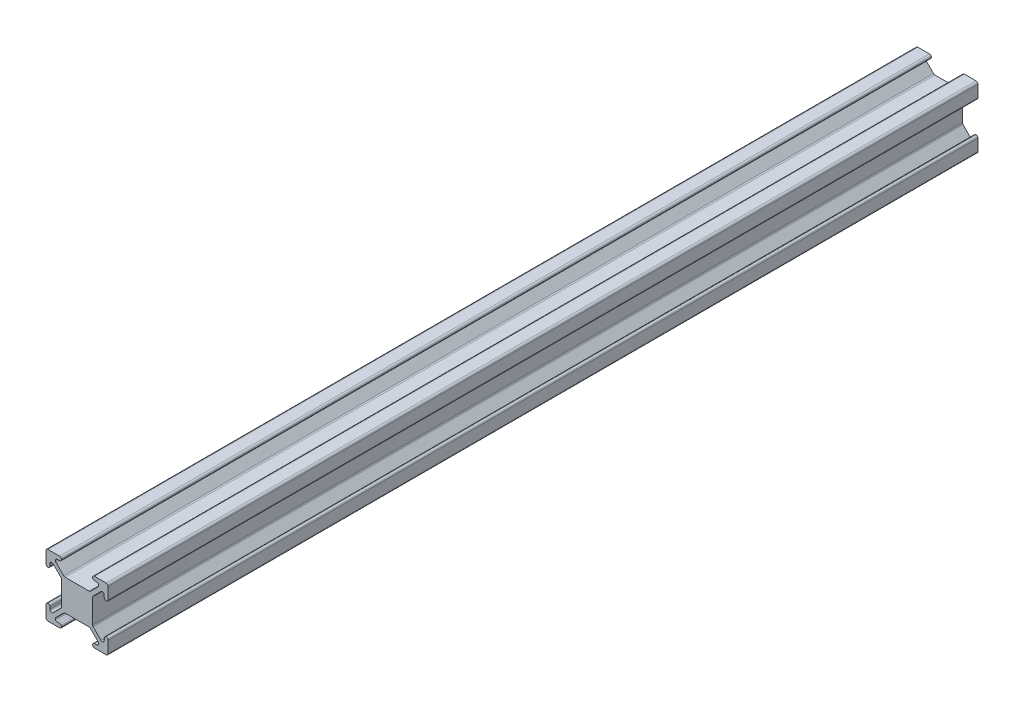
SolidWorks part; units mm, degrees
ref_plane "Front Plane" through (0, 0, 0) normal (0, 0, 1) x (1, 0, 0)
ref_plane "Top Plane" through (0, 0, 0) normal (0, 1, 0) x (1, 0, 0)
ref_plane "Right Plane" through (0, 0, 0) normal (1, 0, 0) x (0, 0, -1)
sketch "Sketch1" plane through (0, 0, 0) normal (0, 0, 1) x (1, 0, 0)
  line L0 (-6.35, -5.2275) -> (-6.35, 5.2275)
  line L1 (-6.35, 5.2275) -> (-11.1125, 9.99)
  line L2 (-11.1125, 9.99) -> (-11.1125, 6.35)
  line L3 (-11.1125, 6.35) -> (-12.7, 6.35)
  line L4 (-12.7, 6.35) -> (-12.7, 12.7)
  line L5 (-12.7, 12.7) -> (-6.35, 12.7)
  line L6 (-6.35, 12.7) -> (-6.35, 11.1125)
  line L7 (-6.35, 11.1125) -> (-9.99, 11.1125)
  line L8 (-9.99, 11.1125) -> (-5.2275, 6.35)
  line L9 (-5.2275, 6.35) -> (5.2275, 6.35)
  line L10 (0, 15.4917) -> (0, -11.1126) construction
  line L11 (-16.3459, 0) -> (7.5931, 0) construction
  line L12 (-5.2275, -6.35) -> (5.2275, -6.35)
  line L13 (-9.99, -11.1125) -> (-5.2275, -6.35)
  line L14 (-6.35, -11.1125) -> (-9.99, -11.1125)
  line L15 (-6.35, -12.7) -> (-6.35, -11.1125)
  line L16 (-12.7, -12.7) -> (-6.35, -12.7)
  line L17 (-12.7, -6.35) -> (-12.7, -12.7)
  line L18 (-11.1125, -6.35) -> (-12.7, -6.35)
  line L19 (-11.1125, -9.99) -> (-11.1125, -6.35)
  line L20 (-6.35, -5.2275) -> (-11.1125, -9.99)
  line L21 (16.3459, 0) -> (-7.5931, 0) construction
  line L22 (6.35, -5.2275) -> (11.1125, -9.99)
  line L23 (11.1125, -9.99) -> (11.1125, -6.35)
  line L24 (11.1125, -6.35) -> (12.7, -6.35)
  line L25 (12.7, -6.35) -> (12.7, -12.7)
  line L26 (12.7, -12.7) -> (6.35, -12.7)
  line L27 (6.35, -12.7) -> (6.35, -11.1125)
  line L28 (6.35, -11.1125) -> (9.99, -11.1125)
  line L29 (9.99, -11.1125) -> (5.2275, -6.35)
  line L30 (9.99, 11.1125) -> (5.2275, 6.35)
  line L31 (6.35, 11.1125) -> (9.99, 11.1125)
  line L32 (6.35, 12.7) -> (6.35, 11.1125)
  line L33 (12.7, 12.7) -> (6.35, 12.7)
  line L34 (12.7, 6.35) -> (12.7, 12.7)
  line L35 (11.1125, 6.35) -> (12.7, 6.35)
  line L36 (11.1125, 9.99) -> (11.1125, 6.35)
  line L37 (6.35, 5.2275) -> (11.1125, 9.99)
  line L38 (6.35, -5.2275) -> (6.35, 5.2275)
  point P19 (-6.35, 0)
  point P37 (0, -6.35)
  point P38 (0, 6.35)
  point P46 (6.35, 0)
  dimension "D1" = 12.7
  dimension "D2" = 12.7
  dimension "D3" = 135
  dimension "D4" = 1.5875
  dimension "D5" = 6.35
  dimension "D6" = 1.5875
  dimension "D7" = 6.35
extrude "Boss-Extrude1" add sketch "Sketch1" against normal blind 355.6
fillet "Fillet1" radius 0.7937 36 edges at (-12.7, -12.7, -177.8) (-6.35, -12.7, -177.8) (-6.35, -11.1125, -177.8) (-11.1125, -6.35, -177.8) (-12.7, -6.35, -177.8) (-11.1125, -9.99, -177.8) (-9.99, -11.1125, -177.8) (-5.2275, -6.35, -177.8) (-6.35, -5.2275, -177.8) (5.2275, -6.35, -177.8) (6.35, -12.7, -177.8) (6.35, -11.1125, -177.8) (9.99, -11.1125, -177.8) (12.7, -12.7, -177.8) (12.7, -6.35, -177.8) (11.1125, -9.99, -177.8) (6.35, -5.2275, -177.8) (12.7, 6.35, -177.8) (11.1125, 9.99, -177.8) (12.7, 12.7, -177.8) (6.35, 12.7, -177.8) (6.35, 11.1125, -177.8) (6.35, 5.2275, -177.8) (5.2275, 6.35, -177.8) (11.1125, 6.35, -177.8) (9.99, 11.1125, -177.8) (11.1125, -6.35, -177.8) (-6.35, 5.2275, -177.8) (-5.2275, 6.35, -177.8) (-12.7, 12.7, -177.8) (-6.35, 12.7, -177.8) (-6.35, 11.1125, -177.8) (-11.1125, 6.35, -177.8) (-12.7, 6.35, -177.8) (-9.99, 11.1125, -177.8) (-11.1125, 9.99, -177.8)
